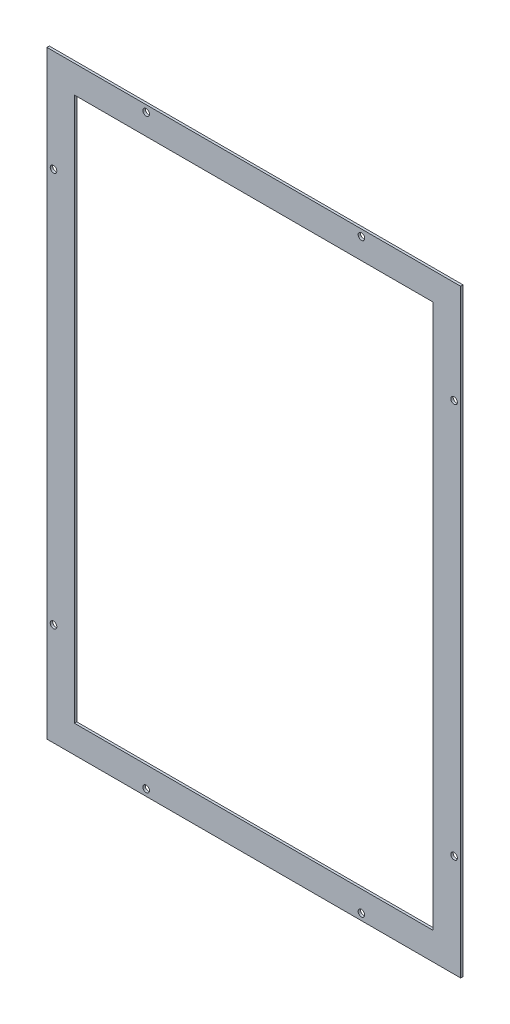
SolidWorks part; units mm, degrees
ref_plane "Ön Düzlem" through (0, 0, 0) normal (0, 0, 1) x (1, 0, 0)
ref_plane "Üst Düzlem" through (0, 0, 0) normal (0, 1, 0) x (1, 0, 0)
ref_plane "Sağ Düzlem" through (0, 0, 0) normal (1, 0, 0) x (0, 0, -1)
sketch "Çizim1" plane through (0, 0, 0) normal (0, 0, 1) x (1, 0, 0)
  line L0 (-150, -455) -> (150, -455)
  line L1 (-150, -455) -> (-150, 0)
  line L2 (-150, 0) -> (150, 0)
  line L3 (150, -455) -> (150, 0)
  line L4 (-173, 23) -> (173, 23)
  line L5 (173, -478) -> (173, 23)
  line L6 (-173, -478) -> (173, -478)
  line L7 (-173, -478) -> (-173, 23)
  point P4 (0, 0)
  dimension "D1" = 455
  dimension "D2" = 300
  dimension "D3" = 23
base flange "Taban-Flanş1" sketch "Çizim1" thickness 2 reverse thickness direction no parameters "D1"=0.7366
sketch "Çizim2" plane through (0, 0, 0) normal (0, 0, 1) x (1, 0, 0)
  line L0 (173, 23) -> (-173, 23) construction
  line L1 (-173, 23) -> (-173, -478) construction
  line L2 (173, -478) -> (173, 23) construction
  line L3 (-173, -478) -> (173, -478) construction
  line L4 (0, 0) -> (0, -148.4818) construction
  line L5 (-150, -227.5) -> (-15.9824, -227.5) construction
  line L6 (-150, 0) -> (-150, -455) construction
  circle A0 centre (90, 17.5) radius 2.75
  circle A1 centre (-90, 17.5) radius 2.75
  circle A2 centre (-167.5, -62.5) radius 2.75
  circle A3 centre (-167.5, -392.5) radius 2.75
  circle A4 centre (167.5, -392.5) radius 2.75
  circle A5 centre (167.5, -62.5) radius 2.75
  circle A6 centre (90, -472.5) radius 2.75
  circle A7 centre (-90, -472.5) radius 2.75
  point P2 (0, 0)
  dimension "D1" = 5.5
  dimension "D6" = 83
  dimension "D3" = 5.5
  dimension "D4" = 83
  dimension "D5" = 5.5
  dimension "D7" = 85.5
  dimension "D8" = 5.5
extrude "Kes-Ekstrüzyon1" cut sketch "Çizim2" against normal blind 10 normal cut yes
sketch "Büküm-Çizgileri1" [suppressed] plane through (0, 0, 0) normal (0, 1, 0) x (1, 0, 0)
sketch "Sınırlandırma-Kutusu1" [suppressed] plane through (0, 0, 0) normal (0, 1, 0) x (1, 0, 0)
sheet metal parameters "Sac-Levha1" thickness 2 parameters "D1"=0.7366
flat pattern "Düz-Çoğaltma1" [suppressed]
sketch "Büküm-Çizgileri2" plane through (0, 0, 0) normal (0, 1, 0) x (1, 0, 0)
sketch3d "Sınırlandırma-Kutusu2" [suppressed]
  line L0 (-173, 23, 0) -> (-173, -478, 0) construction
  line L1 (173, 23, 0) -> (173, -478, 0) construction
  line L2 (-173, 23, 0) -> (173, 23, 0) construction
  line L3 (-173, -478, 0) -> (173, -478, 0) construction
sheet metal parameters "Sac-Levha2" thickness 2 parameters "D1"=0.7366
flat pattern "Düz-Çoğaltma1"
sketch "Büküm-Çizgileri2" plane through (0, 0, 0) normal (0, 1, 0) x (1, 0, 0)
sketch3d "Sınırlandırma-Kutusu2" [suppressed]
  line L0 (173, 23, 0) -> (173, -478, 0) construction
  line L1 (-173, 23, 0) -> (-173, -478, 0) construction
  line L2 (173, 23, 0) -> (-173, 23, 0) construction
  line L3 (173, -478, 0) -> (-173, -478, 0) construction
